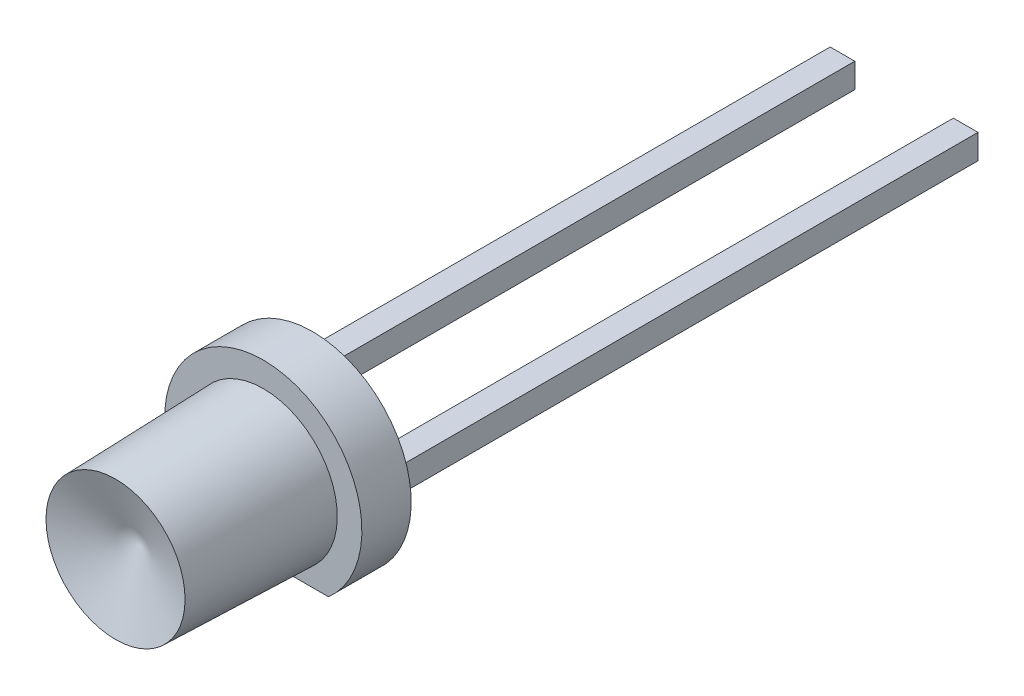
SolidWorks part; units mm, degrees
ref_plane "Front Plane" through (0, 0, 0) normal (0, 0, 1) x (1, 0, 0)
ref_plane "Top Plane" through (0, 0, 0) normal (0, 1, 0) x (1, 0, 0)
ref_plane "Right Plane" through (0, 0, 0) normal (1, 0, 0) x (0, 0, -1)
sketch "Sketch1" plane through (0, 0, 0) normal (0, 0, 1) x (1, 0, 0)
  line L1 (0, 0) -> (-0.5, 0)
  line L2 (0, 0) -> (0, -0.5)
  line L3 (0, -0.5) -> (-0.5, -0.5)
  line L4 (-0.5, 0) -> (-0.5, -0.5)
  line L5 (2, 0) -> (2, -0.5)
  line L6 (2, -0.5) -> (2.5, -0.5)
  line L7 (2.5, -0.5) -> (2.5, 0)
  line L8 (2.5, 0) -> (2, 0)
extrude "Boss-Extrude1" add sketch "Sketch1" along normal blind 10 and the other way blind 2
sketch "Sketch2" plane through (0, 0, 10) normal (0, 0, 1) x (1, 0, 0)
  circle A0 centre (1, -0.25) radius 2
extrude "Boss-Extrude2" add sketch "Sketch2" along normal blind 1
sketch "Sketch5" plane through (0, 0, 10) normal (0, 0, -1) x (-1, 0, 0)
  line L0 (-1, -1.75) -> (-2.3229, -1.75)
  line L1 (-2.3229, -1.75) -> (0.3229, -1.75)
  arc A0 (-2.3229, -1.75) -> (0.3229, -1.75) centre (-1, -0.25) ccw
  circle M5 centre (-1, -0.25) radius 2
extrude "Cut-Extrude1" cut sketch "Sketch5" against normal blind 3 contours L1 L0 M5 region at (1, -1.9523, 10)
ref_axis "Axis1" through (1, -1.75, 11) along (0, 1, 0)
ref_axis "Axis2" through (1, -1.75, 10) along (0, 1, 0)
ref_plane "Plane2" through (1, 0, 0) normal (1, 0, 0) x (0, 0, -1)
sketch "Sketch9" plane through (1, 0, 0) normal (1, 0, 0) x (0, 0, -1)
  line L0 (-13.9987, -1.6626) -> (-13.5, -0.2519)
  line L1 (-11, 1.2481) -> (-11, -1.7519)
  line L2 (-11, -1.7519) -> (-11, 1.2481)
  line L3 (-11, -0.2519) -> (-13.5, -0.2519)
  line L4 (-11, -1.7519) -> (-13.9987, -1.6626)
revolve "Revolve6" add sketch "Sketch9" angle 360 about L3 region at (1, -1.0024, 12.3658)
